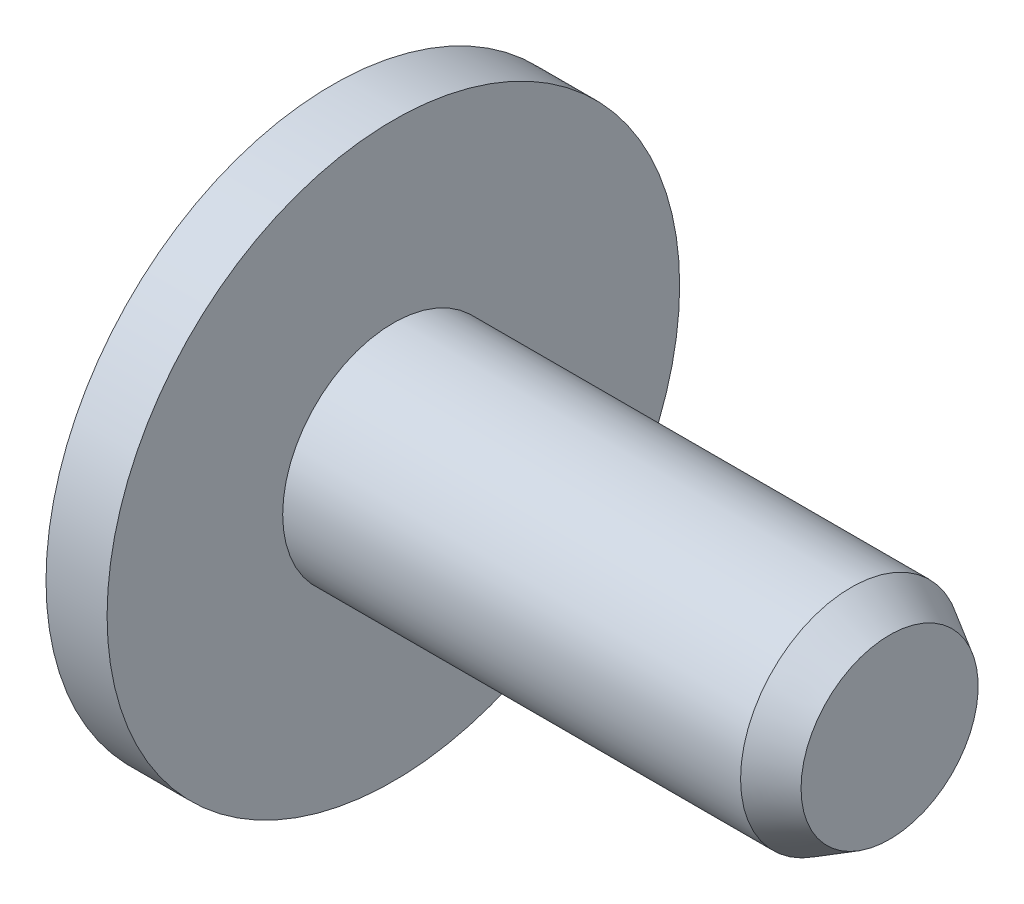
SolidWorks part; units mm, degrees
ref_plane "Front" through (0, 0, 0) normal (0, 0, 1) x (1, 0, 0)
ref_plane "Top" through (0, 0, 0) normal (0, 1, 0) x (1, 0, 0)
ref_plane "Right" through (0, 0, 0) normal (1, 0, 0) x (0, 0, -1)
sketch "Sketch1" plane through (0, 0, 0) normal (0, 0, 1) x (1, 0, 0)
  line L0 (0, 3.75) -> (0, 1.45)
  line L1 (0, 1.45) -> (6.5, 1.45)
  line L2 (6.5, 1.45) -> (6.5, 0)
  line L3 (0, 3.75) -> (-0.8, 3.75)
  line L4 (-0.8, 3.75) -> (-0.8, 3.0623)
  line L5 (-2.35, 0) -> (-2.35, -1.3041) construction
  line L7 (-6.4783, 0) -> (12.5724, 0) construction
  line L8 (-2.35, 0) -> (6.5, 0)
  arc A0 (-0.8, 3.0623) -> (-2.35, 0) centre (1.45, 0) ccw
revolve "Revolve1" add sketch "Sketch1" angle 360 about L7
cosmetic thread "ThreadCosmetic" [suppressed] parameters "D2"=1.4
chamfer "Chamfer1" distance 0.29 angle 60 1 edges at (6.5, 0, 1.45) first distance on face at (6.5, 0, 1.45)
sketch "Sketch9" plane through (0, 0, 0) normal (0, 0, 1) x (1, 0, 0)
  line L0 (0.096, 0.7) -> (0.4811, 0.7)
  line L1 (0.4811, 0.7) -> (0.0481, 1.45)
  line L2 (0.096, 0.7) -> (0.529, 1.45)
  line L3 (0.0481, 1.45) -> (0.0481, 1.7)
  line L4 (0.529, 1.45) -> (0.529, 1.7)
  line L5 (0.0481, 1.7) -> (0.529, 1.7)
  line L6 (0.2886, 0.7) -> (0.2886, 0) construction
  line L7 (0, 0) -> (7.3035, 0) construction
  line L8 (0, -1.45) -> (0, 1.45) construction
  line L10 (0, -3.75) -> (0, 3.75) construction
  line L11 (5.9977, 1.45) -> (0, 1.45) construction
  dimension "D2" = 60
  dimension "D3" = 0.25
revolve "ThreadSchematic" [suppressed] cut sketch "Sketch9" angle 360 about L7
pattern_linear "ThdSchPat" [suppressed] count 14 spacing 0.4809 along (1, 0, 0) of bodies 144
sketch "Sketch2" plane through (0, 0, 0) normal (0, 0, 1) x (1, 0, 0)
  line L0 (6.5, 1.45) -> (6.5, 0) construction
  line L1 (6.5, 0) -> (6.5, 1.0614) construction
  line L2 (0, 0) -> (8.4194, 0) construction
  line L5 (6.2098, -0.4431) -> (3.9, -1.45)
  line L7 (3.9, -1.45) -> (3.9, -1.65)
  line L8 (3.9, -1.65) -> (6.7, -1.65)
  line L9 (6.7, -1.65) -> (6.7, 0)
  line L10 (6.7, 0) -> (6.5, 0)
  arc A0 (6.2098, -0.4431) -> (6.5, 0) centre (6.0167, 0) ccw
  point P6 (0, -1.45)
  dimension "D1" = 0.4833
  dimension "D2" = 0.2
  dimension "D3" = 0.2
revolve "EndRound" [suppressed] cut sketch "Sketch2" angle 360 about L2
sketch "Sketch8" plane through (0, 0, 0) normal (0, 0, 1) x (1, 0, 0)
  line L0 (6.5, 0) -> (6.7, 0)
  line L1 (-6.4783, 0) -> (12.5724, 0) construction
  line L2 (6.7, 0) -> (6.7, -1.65)
  line L3 (6.7, -1.65) -> (3.9, -1.65)
  line L4 (3.9, -1.65) -> (3.9, -1.45)
  line L6 (3.9, -1.45) -> (6.5, 0)
  line L7 (0, 0) -> (9.5575, 0) construction
  line L8 (0, -1.45) -> (11.5982, -1.45) construction
  dimension "yc" = 2.6
  dimension "D2" = 0.2
  dimension "D3" = 0.2
revolve "EndCone" [suppressed] cut sketch "Sketch8" angle 360 about L7
ref_plane "Plane1" through (-2.35, 0, 0) normal (1, 0, 0) x (0, 0, -1)
sketch "Sketch4" plane through (-2.35, 0, 0) normal (1, 0, 0) x (0, 0, -1)
  line L0 (0.3, 1.5) -> (-0.3, 1.5)
  line L1 (-0.3, 1.5) -> (-0.3, 0.3)
  line L2 (-0.3, 0.3) -> (-1.5, 0.3)
  line L3 (-1.5, 0.3) -> (-1.5, -0.3)
  line L4 (-1.5, -0.3) -> (-0.3, -0.3)
  line L5 (-0.3, -0.3) -> (-0.3, -1.5)
  line L6 (-0.3, -1.5) -> (0.3, -1.5)
  line L7 (0.3, -1.5) -> (0.3, -0.3)
  line L8 (0.3, -0.3) -> (1.5, -0.3)
  line L9 (1.5, -0.3) -> (1.5, 0.3)
  line L10 (1.5, 0.3) -> (0.3, 0.3)
  line L11 (0.3, 0.3) -> (0.3, 1.5)
  line L12 (1.5, 0) -> (-1.5, 0) construction
  dimension "D2" = 0.6
extrude "Cut-Extrude1" cut sketch "Sketch4" along normal blind 1.58
draft "Draft1" type of draft neutral plane draft angle 35 neutral plane "Plane1" faces to draft 4 face at (-1.4025, 0, -1.5) face at (-1.4025, -1.5, 0) face at (-1.4025, 0, 1.5) face at (-1.4025, 1.5, 0) neutral plane through (-2.35, 0, 0) neutral plane normal (1, 0, 0) reverse direction yes parameters "D1"=35
draft "Draft2" type of draft neutral plane draft angle 8 neutral plane "Plane1" faces to draft 8 face at (-1.5002, 0.5815, -0.3) face at (-1.5002, 0.3, -0.5815) face at (-1.5002, -0.3, -0.5815) face at (-1.5002, -0.5815, -0.3) face at (-1.5002, -0.5815, 0.3) face at (-1.5002, -0.3, 0.5815) face at (-1.5002, 0.3, 0.5815) face at (-1.5002, 0.5815, 0.3) neutral plane through (-2.35, 0, 0) neutral plane normal (1, 0, 0) reverse direction yes parameters "D1"=8
fillet "Fillet1" radius 0.25 4 edges at (-1.5484, -0.1873, -0.1873) (-1.5484, -0.1873, 0.1873) (-1.5484, 0.1873, 0.1873) (-1.5484, 0.1873, -0.1873)
sketch "Sketch7" plane through (-2.35, 0, 0) normal (1, 0, 0) x (0, 0, -1)
  line L0 (-0.265, 1.3259) -> (-1.3259, 1.3259) construction
  line L1 (-1.3259, 1.3259) -> (-1.3259, 0.265) construction
  line L2 (0, 0) -> (-1.3259, 1.3259) construction
  line L3 (-0.0779, 0.3255) -> (-1.3259, 1.3259)
  line L4 (-1.3259, 1.3259) -> (-0.3255, 0.0779)
  line L5 (-0.3255, 0.0779) -> (-0.3255, 0)
  line L6 (-0.0779, 0.3255) -> (0, 0.3255)
  line L7 (0.0779, 0.3255) -> (0, 0.3255)
  line L8 (1.3259, 1.3259) -> (0.0779, 0.3255)
  line L9 (0.3255, 0.0779) -> (1.3259, 1.3259)
  line L10 (0.3255, 0.0779) -> (0.3255, 0)
  line L11 (0.3255, -0.0779) -> (0.3255, 0)
  line L12 (1.3259, -1.3259) -> (0.3255, -0.0779)
  line L13 (0.0779, -0.3255) -> (1.3259, -1.3259)
  line L14 (0.0779, -0.3255) -> (0, -0.3255)
  line L15 (-0.0779, -0.3255) -> (0, -0.3255)
  line L16 (-1.3259, -1.3259) -> (-0.0779, -0.3255)
  line L17 (-0.3255, -0.0779) -> (-1.3259, -1.3259)
  line L18 (-0.3255, -0.0779) -> (-0.3255, 0)
extrude "TypeZ" [suppressed] cut sketch "Sketch7" along normal blind 0.316 draft 2
equation "\"minordia@Sketch9\" = \"D2@ThreadCosmetic\""
equation "\"D1@Chamfer1\" = \"d@Sketch1\" / 10"
equation "\"D1@Sketch2\" = \"d@Sketch1\" / 6"
equation "\"D2@Sketch4\" = \"m@Sketch4\" / 5"
equation "\"D1@TypeZ\" = \"depth@Cut-Extrude1\" * 0.2"
equation "\"D1@Fillet1\" =\"m@Sketch4\" /12"
equation "\"threadstart@Sketch9\" = \"advance@Sketch9\" * 0.6"
equation "\"D1@ThdSchPat\" = int((\"l@Sketch1\"/\"advance@Sketch9\") + 0.999)"
equation "\"D3@ThdSchPat\" = \"advance@Sketch9\""
